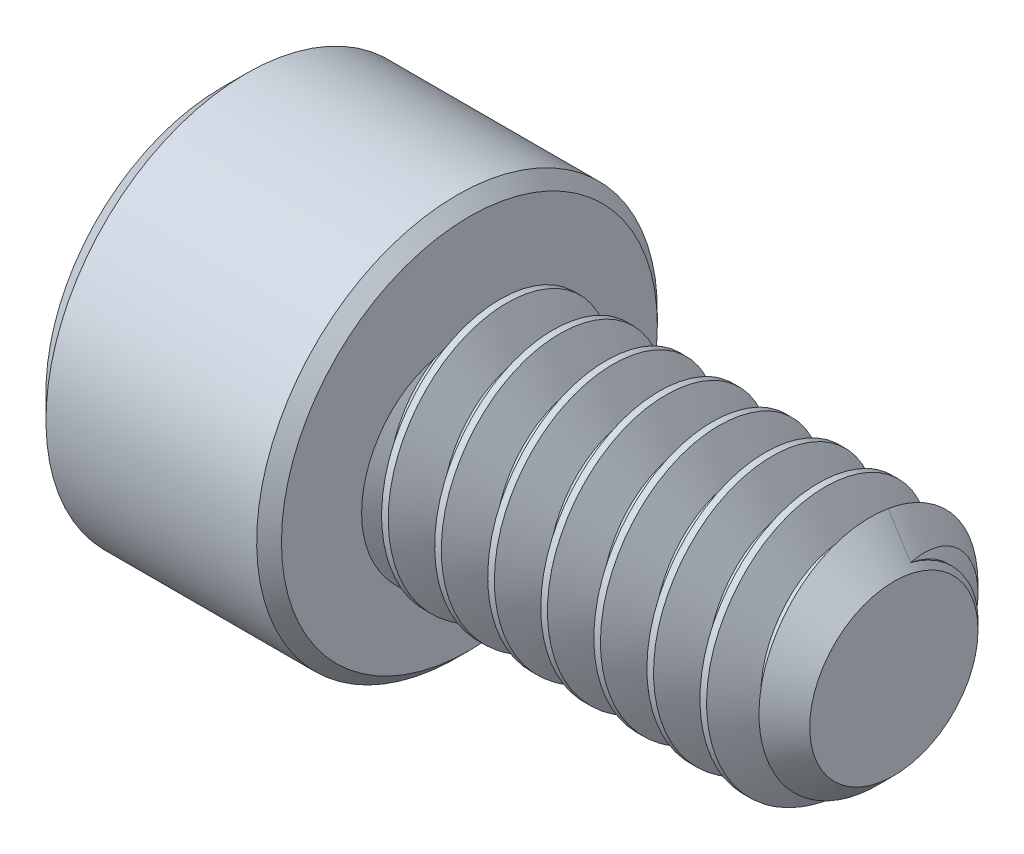
SolidWorks part; units mm, degrees
ref_plane "Front Plane" through (0, 0, 0) normal (0, 0, 1) x (1, 0, 0)
ref_plane "Top Plane" through (0, 0, 0) normal (0, 1, 0) x (1, 0, 0)
ref_plane "Right Plane" through (0, 0, 0) normal (1, 0, 0) x (0, 0, -1)
sketch "Sketch1" plane through (0, 0, 0) normal (0, 0, 1) x (1, 0, 0)
  line L0 (1.5875, 0) -> (-1.5875, 0) construction
  line L1 (1.5875, 0.9271) -> (1.5875, -0.9271) construction
  line L2 (-1.5875, 1.4059) -> (-1.5875, -1.4059) construction
  line L3 (-1.6802, 1.4986) -> (-3.2563, 1.4986) construction
  line L4 (-3.2563, 1.4986) -> (-3.4417, 1.3132) construction
  line L5 (-3.4417, 1.3132) -> (-3.4417, -1.3132) construction
  line L6 (-3.4417, -1.3132) -> (-3.2563, -1.4986) construction
  line L7 (-3.2563, -1.4986) -> (-1.6802, -1.4986) construction
  line L8 (-1.6802, 1.4986) -> (-1.5875, 1.4059) construction
  line L9 (-1.5875, -1.4059) -> (-1.6802, -1.4986) construction
  point P5 (-1.5875, 1.4986)
  point P6 (-1.5875, -1.4986)
  point P7 (-2.6543, 0)
  point P12 (0, -0.9271)
  dimension "D1" = 45
  dimension "Dec." = 1.8542
  dimension "Length" = 3.175
  dimension "Head Dia" = 2.9972
  dimension "Head Height" = 1.8542
  dimension "Hex Depth" = 0.7874
  dimension "Chamfer" = 0.1854
  dimension "D2" = 1.5875
  dimension "D3" = 0.0927
  dimension "D4" = 45
ref_plane "Plane1" through (1.5875, 0, 0) normal (1, 0, 0) x (0, 0, -1)
ref_plane "Plane2" through (-3.4417, 0, 0) normal (1, 0, 0) x (0, 0, -1)
sketch "Sketch2" plane through (1.5875, 0, 0) normal (1, 0, 0) x (0, 0, -1)
  circle A0 centre (0, 0) radius 0.9271
extrude "Boss-Extrude1" add sketch "Sketch2" against normal up to vertex (3.175 mm away) up to point (-1.5875, 0, 0)
sketch "Sketch3" plane through (1.5875, 0, 0) normal (1, 0, 0) x (0, 0, -1)
  circle A0 centre (0, 0) radius 0.9271 construction
  circle A1 centre (0, 0) radius 0.9271
curve "Helix/Spiral1" pitch 0.3969 height 3.5719 radius 0.9271 centre (1.5875, 0, 0) axis (-1, 0, 0) start towards (0, 1, 0) parameters "Pitch"=0.3969
chamfer "Chamfer1" distance 0.2977 angle 45 1 edges at (1.5875, 0, -0.9271)
sketch "Sketch5" plane through (0, 0, 0) normal (0, 0, 1) x (1, 0, 0)
  line L0 (1.4139, 0.9271) -> (1.7611, 0.9271)
  line L1 (1.7611, 0.9271) -> (1.6123, 0.6693)
  line L2 (1.6123, 0.6693) -> (1.5627, 0.6693)
  line L3 (1.5627, 0.6693) -> (1.4139, 0.9271)
  line L4 (1.5875, 0.6693) -> (1.5875, 0.9271) construction
  line L5 (1.4883, 0.7982) -> (1.6867, 0.7982) construction
  dimension "D1" = 60
  dimension "D2" = 0.1984
  dimension "D3" = 0.0496
sweep "Cut-Sweep1" cut profiles "Sketch5" path "Helix/Spiral1" align with end faces yes
sketch "Sketch4" plane through (-3.4417, 0, 0) normal (1, 0, 0) x (0, 0, -1)
  line L0 (-1.4986, 0.7937) -> (1.4986, 0.7937) construction
  line L1 (0, 0.9165) -> (-0.7937, 0.4583)
  line L2 (-0.7937, 0.4583) -> (-0.7937, -0.4583)
  line L3 (-0.7937, -0.4583) -> (0, -0.9165)
  line L4 (0, -0.9165) -> (0.7937, -0.4583)
  line L5 (0.7937, -0.4583) -> (0.7937, 0.4583)
  line L6 (0.7937, 0.4583) -> (0, 0.9165)
  line L7 (0, 0) -> (0, 0.7937) construction
  circle A0 centre (0, 0) radius 0.7937 construction
  dimension "Hex Size" = 1.5875
  dimension "D1" = 2.9972
  dimension "D2" = 0.7937
sketch "Sketch6" plane through (0, 0, 0) normal (0, 0, 1) x (1, 0, 0)
  line L0 (-3.2563, 1.4986) -> (-3.4417, 1.3132) construction
  line L2 (-1.5875, 1.4059) -> (-1.5875, -1.4059) construction
  line L3 (-3.4417, 1.3132) -> (-3.4417, -1.3132) construction
  line L4 (-3.2563, 1.4986) -> (-3.4417, 1.3132)
  line L5 (-1.6802, 1.4986) -> (-3.2563, 1.4986) construction
  line L6 (-1.5875, 1.4059) -> (-1.5875, 0)
  line L7 (-3.4417, 1.3132) -> (-3.4417, 0)
  line L8 (-1.5875, 0) -> (-3.4417, 0) construction
  line L9 (-1.5875, 0) -> (-3.4417, 0)
  line L10 (-1.6802, 1.4986) -> (-1.5875, 1.4059) construction
  line L11 (-1.6802, 1.4986) -> (-3.2563, 1.4986)
  line L12 (-1.6802, 1.4986) -> (-1.5875, 1.4059)
revolve "Revolve1" add sketch "Sketch6" angle 360 about L8
extrude "Cut-Extrude1" cut sketch "Sketch4" along normal up to vertex (0.7874 mm away) up to point (-2.6543, 0, 0)
sketch "Sketch8" plane through (-3.4417, 0, 0) normal (-1, 0, 0) x (0, 0, 1)
  circle A1 centre (0, 0) radius 0.9165
extrude "Cut-Extrude2" cut sketch "Sketch8" against normal blind 0.3708 draft 45
equation "\"D3@Helix/Spiral1\" = \"Length@Sketch1\"+\"Pitch@Helix/Spiral1\""
equation "\"D3@Sketch5\" = \"Pitch@Helix/Spiral1\"*.125"
equation "\"D2@Sketch5\" = \"Pitch@Helix/Spiral1\"*.50"
equation "\"D1@Chamfer1\" = \"Pitch@Helix/Spiral1\"*.75"
equation "\"D2@Sketch1\" = \"Pitch@Helix/Spiral1\"*4"
equation "\"D1@Sketch4\" = \"Head Dia@Sketch1\""
equation "\"Chamfer@Sketch1\" = \"Head Height@Sketch1\"/10"
equation "\"D3@Sketch1\" = \"Chamfer@Sketch1\"/2"
equation "\"D1@Cut-Extrude2\" = \"Chamfer@Sketch1\"*2"
